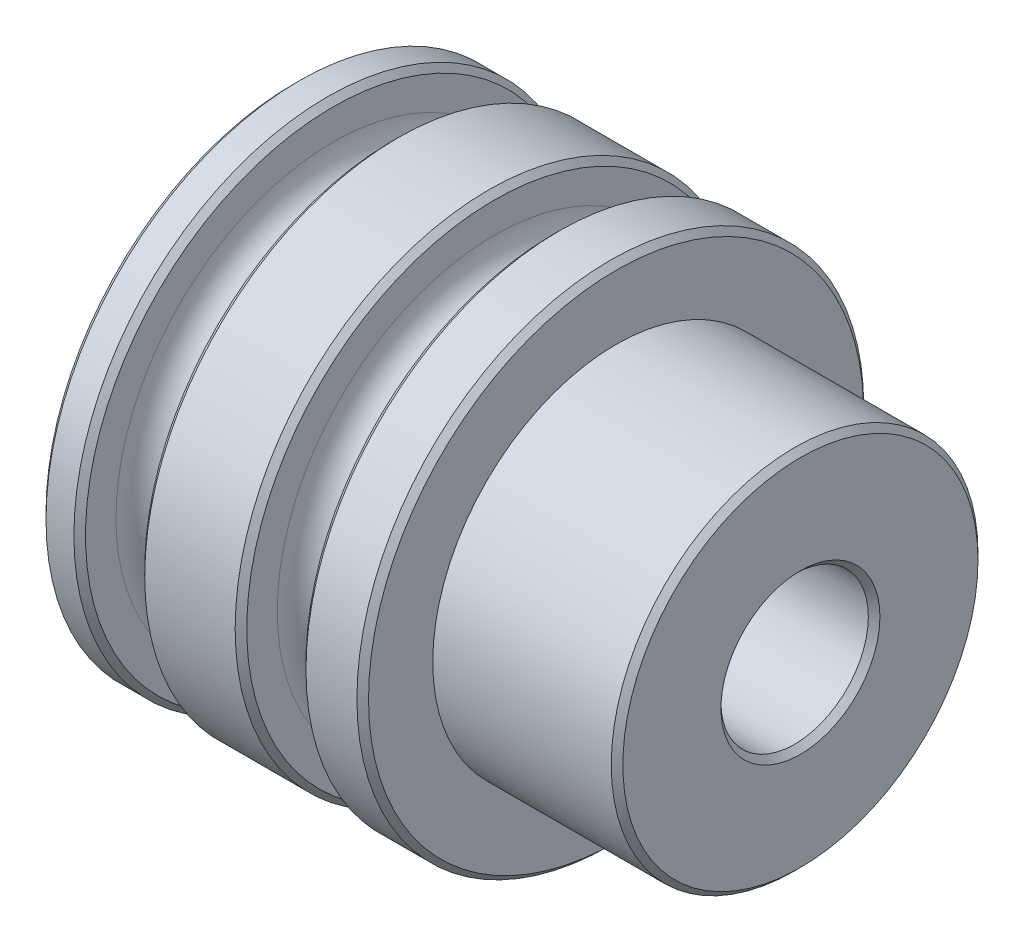
SolidWorks part; units mm, degrees
material "Nylon 101"
ref_plane "Front Plane" through (0, 0, 0) normal (0, 0, 1) x (1, 0, 0)
ref_plane "Top Plane" through (0, 0, 0) normal (0, 1, 0) x (1, 0, 0)
ref_plane "Right Plane" through (0, 0, 0) normal (1, 0, 0) x (0, 0, -1)
sketch "Sketch1" plane through (0, 0, 0) normal (1, 0, 0) x (0, 0, -1)
  circle A0 centre (0, 0) radius 12.6365
  dimension "D1" = 25.273
extrude "Boss-Extrude1" add sketch "Sketch1" along normal blind 12.7
sketch "Sketch2" plane through (0, 0, 0) normal (-1, 0, 0) x (0, 0, 1)
  circle A0 centre (0, 0) radius 17.4625
  dimension "D1" = 34.925
extrude "Boss-Extrude2" add sketch "Sketch2" along normal blind 22.225
sketch "Sketch3" plane through (-22.225, 0, 0) normal (-1, 0, 0) x (0, 0, 1)
  circle A0 centre (0, 0) radius 11.1125
  dimension "D1" = 22.225
extrude "Cut-Extrude1" cut sketch "Sketch3" against normal blind 7.112
sketch "Sketch4" plane through (-15.113, 0, 0) normal (-1, 0, 0) x (0, 0, 1)
  circle A0 centre (0, 0) radius 7.2746
  dimension "D1" = 14.5492
extrude "Cut-Extrude2" cut sketch "Sketch4" against normal blind 0.2
sketch "Sketch5" plane through (-14.913, 0, 0) normal (-1, 0, 0) x (0, 0, 1)
  circle A0 centre (0, 0) radius 5.08
  dimension "D1" = 10.16
extrude "Cut-Extrude3" cut sketch "Sketch5" against normal through all
sketch "Sketch6" plane through (0, 0, 0) normal (0, 0, 1) x (1, 0, 0)
  line L0 (-8.39, 17.4625) -> (-8.39, 14.9625)
  line L1 (0, 17.4625) -> (-22.225, 17.4625) construction
  line L2 (-4.31, 17.4625) -> (-4.31, 14.9625)
  line L3 (-6.35, 12.9225) -> (-6.35, 0) construction
  line L4 (-6.35, 14.9625) -> (-6.35, 17.4625) construction
  line L5 (-8.39, 17.4625) -> (-4.31, 17.4625)
  line L6 (-8.39, 17.4625) -> (-4.31, 17.4625)
  line L7 (-6.35, 0) -> (0, 0) construction
  line L8 (0, -17.4625) -> (0, 17.4625) construction
  arc A0 (-8.39, 14.9625) -> (-4.31, 14.9625) centre (-6.35, 14.9625) ccw
  dimension "D1" = 2.04
  dimension "D2" = 12.9225
  dimension "D3" = 2.5
  dimension "D4" = 6.35
revolve "Cut-Revolve1" cut sketch "Sketch6" angle 360 about L7 region at (-6.35, 15.3861, 0)
pattern_linear "LPattern1" count 2 spacing 11.1125 along (-1, 0, 0) of "Cut-Revolve1"
chamfer "Chamfer1" distance 0.4 angle 45 9 edges at (12.7, 0, -12.6365) (12.7, 0, 5.08) (-22.225, 0, 17.4625) (-22.225, 0, 11.1125) (-19.5025, 0, 17.4625) (-8.39, 0, 17.4625) (-15.4225, 0, 17.4625) (0, 0, 17.4625) (-4.31, 0, 17.4625)
equation "\"D1@Sketch6\"=2mm+.04mm"
equation "\"D2@Sketch6\"=19mm/2"
equation "\"D3@Sketch6\"=2.5mm"
